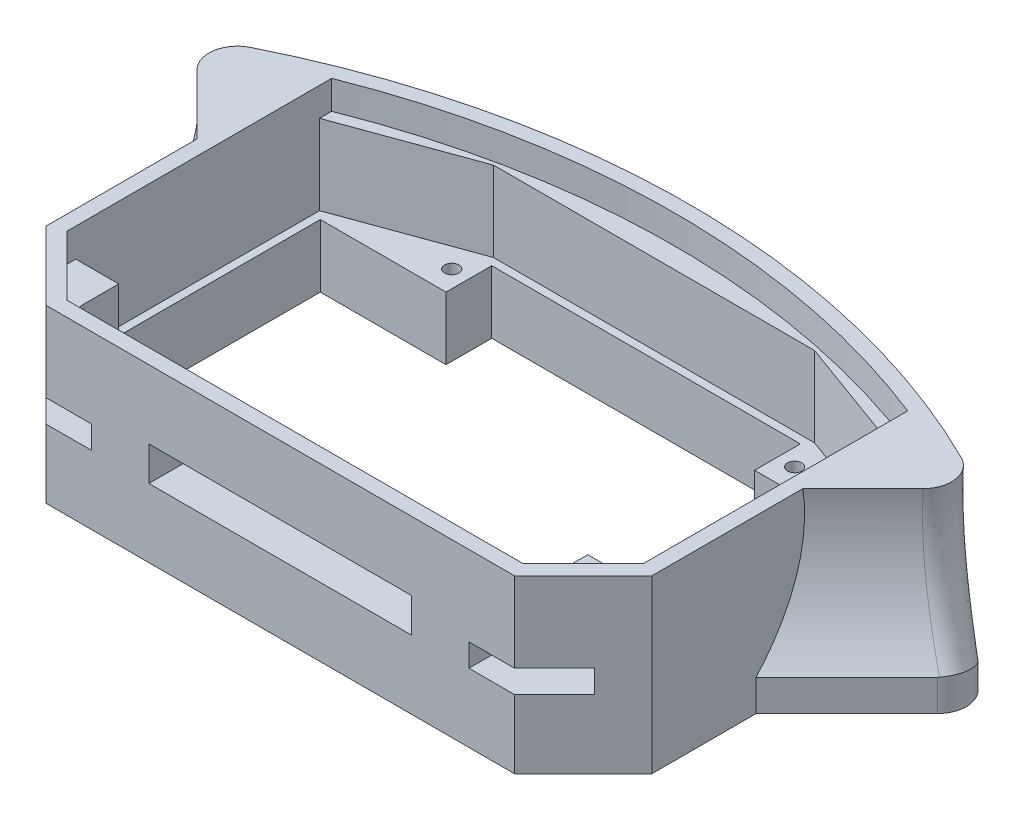
SolidWorks part; units mm, degrees
ref_plane "Front Plane" through (0, 0, 0) normal (0, 0, 1) x (1, 0, 0)
ref_plane "Top Plane" through (0, 0, 0) normal (0, 1, 0) x (1, 0, 0)
ref_plane "Right Plane" through (0, 0, 0) normal (1, 0, 0) x (0, 0, -1)
sketch "Sketch1" plane through (0, 0, 0) normal (0, 1, 0) x (1, 0, 0)
  line L0 (53, 80) -> (53, 129.1478)
  line L1 (-53, 129.1478) -> (-53, 80)
  line L2 (-41, 68) -> (41, 68)
  line L3 (-53, 80) -> (-41, 68)
  line L4 (41, 68) -> (53, 80)
  circle A0 centre (0, 0) radius 140 construction
  arc A1 (53, 129.1478) -> (-53, 129.1478) centre (0, 0) ccw
  dimension "D1" = 280
  dimension "D3" = 139.6
  dimension "D2" = 106
  dimension "D4" = 68
  dimension "D5" = 80
  dimension "D6" = 135
  dimension "D7" = 135
extrude "Boss-Extrude1" add sketch "Sketch1" along normal blind 30
sketch "Sketch2" plane through (0, 30, 0) normal (0, 1, 0) x (1, 0, 0)
  line L0 (-49, 84) -> (49, 84)
  line L1 (49, 84) -> (49, 124)
  line L2 (49, 124) -> (27, 124)
  line L3 (27, 124) -> (27, 132)
  line L4 (27, 132) -> (-27, 132)
  line L5 (-27, 132) -> (-27, 124)
  line L6 (-27, 124) -> (-49, 124)
  line L7 (-49, 124) -> (-49, 84)
  line L12 (-53, 129.1478) -> (-53, 80) construction
  dimension "D1" = 48
  dimension "D2" = 98
  dimension "D3" = 8
  dimension "D4" = 84
  dimension "D5" = 22
  dimension "D6" = 4
extrude "Cut-Extrude1" cut sketch "Sketch2" against normal up to next
sketch "Sketch3" plane through (0, 30, 0) normal (0, 1, 0) x (1, 0, 0)
  line L0 (-50, 83) -> (50, 83) construction
  line L1 (50, 83) -> (50, 125) construction
  line L2 (50, 125) -> (28, 133) construction
  line L3 (28, 133) -> (-28, 133) construction
  line L4 (-28, 133) -> (-50, 125) construction
  line L5 (-50, 125) -> (-50, 83) construction
  line L7 (-49, 84) -> (-49, 124) construction
  line L8 (-50.4, 125.2802) -> (-50.4, 82.6)
  line L9 (-50.4, 82.6) -> (50.4, 82.6)
  line L10 (50.4, 82.6) -> (50.4, 125.2802)
  line L11 (50.4, 125.2802) -> (28.0705, 133.4)
  line L12 (28.0705, 133.4) -> (-28.0705, 133.4)
  line L13 (-28.0705, 133.4) -> (-50.4, 125.2802)
  line L16 (-49, 84) -> (49, 84) construction
  dimension "D1" = 50
  dimension "D2" = 22
  dimension "D3" = 8
  dimension "D4" = 1
  dimension "D5" = 1
  dimension "D6" = 100
  dimension "D7" = 0.4
extrude "Cut-Extrude2" cut sketch "Sketch3" against normal offset from surface (19 mm away) 11 up to face at (0, 0, -116)
sketch "Sketch5" plane through (0, 30, 0) normal (0, 1, 0) x (1, 0, 0)
  line L1 (-42.48, 71.91) -> (38.8, 71.91) construction
  line L2 (-42.48, 71.91) -> (-42.48, 125.25) construction
  line L3 (-42.48, 125.25) -> (38.8, 125.25) construction
  line L4 (38.8, 71.91) -> (38.8, 125.25) construction
  line L6 (-42.88, 71.51) -> (-42.88, 125.65)
  line L7 (-42.88, 125.65) -> (39.2, 125.65)
  line L8 (39.2, 71.51) -> (39.2, 125.65)
  line L9 (-42.88, 71.51) -> (39.2, 71.51)
  dimension "D1" = 71.91
  dimension "D2" = 38.8
  dimension "D3" = 81.28
  dimension "D4" = 53.34
  dimension "D5" = 0.4
extrude "Cut-Extrude4" cut sketch "Sketch5" against normal offset from surface (12.4 mm away) 17.6 up to face at (0, 0, -116)
sketch "Sketch4" plane through (0, 17.6, 0) normal (0, 1, 0) x (1, 0, 0)
  circle A0 centre (26.18, 74.72) radius 1.25
  circle A1 centre (-27.53, 74.72) radius 1.25
  dimension "D2" = 2.5
  dimension "D1" = 27.53
  dimension "D3" = 5.28
  dimension "D4" = 26.18
extrude "Cut-Extrude3" cut sketch "Sketch4" against normal blind 15
fillet "Fillet1" radius 5 2 edges at (39.2, 23.8, -71.51) (-42.88, 23.8, -71.51)
sketch "Sketch6" plane through (0, 30, 0) normal (0, 1, 0) x (1, 0, 0)
  line L20 (50.4, 81.077) -> (50.4, 127.3925)
  line L21 (39.923, 70.6) -> (50.4, 81.077)
  line L22 (-39.923, 70.6) -> (39.923, 70.6)
  line L23 (-50.4, 81.077) -> (-39.923, 70.6)
  line L24 (-50.4, 127.3925) -> (-50.4, 81.077)
  line L25 (50.4, 81.077) -> (50.4, 127.3925)
  line L26 (39.923, 70.6) -> (50.4, 81.077)
  line L27 (-39.923, 70.6) -> (39.923, 70.6)
  line L28 (-50.4, 81.077) -> (-39.923, 70.6)
  line L29 (-50.4, 127.3925) -> (-50.4, 81.077)
  arc A7 (50.4, 127.3925) -> (-50.4, 127.3925) centre (0, 0) ccw
  arc A8 (50.4, 127.3925) -> (-50.4, 127.3925) centre (0, 0) ccw
  dimension "D1" = 2.6
extrude "Cut-Extrude5" cut sketch "Sketch6" against normal blind 5
sketch "Sketch7" plane through (0, 0, 0) normal (0, -1, 0) x (1, 0, 0)
  line L0 (73.4563, -118.7111) -> (53, -98.2548)
  line L1 (53, -80) -> (53, -129.1478) construction
  line L2 (53, -98.2548) -> (53, -129.1478)
  line L3 (0, 0) -> (103.3995, -103.3995) construction
  arc A0 (53, -129.1478) -> (73.4563, -118.7111) centre (0, 0) ccw
  arc A1 (-53, -129.1478) -> (53, -129.1478) centre (0, 0) ccw construction
  dimension "D1" = 45
  dimension "D2" = 32
extrude "Boss-Extrude2" add sketch "Sketch7" against normal up to surface (30 mm away) up to face at (0, 30, -94.6244)
ref_plane "Plane1" through (96.0837, 0, -96.0837) normal (-0.7071, 0, 0.7071) x (0, -1, 0)
sketch "Sketch8" plane through (96.0837, 0, -96.0837) normal (-0.7071, 0, 0.7071) x (0, -1, 0)
  line L0 (-30, -32) -> (0, -32) construction
  circle A0 centre (-26, 0) radius 38
  dimension "D3" = 76
  dimension "D1" = 32
  dimension "D2" = 26
extrude "Cut-Extrude6" cut sketch "Sketch8" along normal up to surface (98.9296 mm away) up to face at (53, 18.75, -84.5637)
mirror "Mirror1" about plane through (0, 0, 0) normal (1, 0, 0) of "Boss-Extrude2"
ref_plane "Plane2" through (-96.0837, 0, -96.0837) normal (0.7071, 0, 0.7071) x (0, -1, 0)
sketch "Sketch9" plane through (-96.0837, 0, -96.0837) normal (0.7071, 0, 0.7071) x (0, -1, 0)
  line L0 (-30, 32) -> (0, 32) construction
  circle A0 centre (-26, 0) radius 38
  dimension "D1" = 76
  dimension "D2" = 32
  dimension "D3" = 26
extrude "Cut-Extrude7" cut sketch "Sketch9" along normal up to surface (22.9296 mm away) up to face at (-53, 18.75, -93.6911)
fillet "Fillet2" radius 5 4 edges at (69.0949, 16.9868, -121.3015) (73.4563, 2.753, -118.7111) (-73.4563, 2.753, -118.7111) (-68.9598, 17.6248, -121.3784)
sketch "Sketch10" plane through (0, 0, -68) normal (0, 0, 1) x (1, 0, 0)
  line L0 (-41, 0) -> (41, 0) construction
  line L1 (-48, 16) -> (-33, 16)
  line L2 (-48, 16) -> (-48, 12)
  line L3 (-48, 12) -> (-33, 12)
  line L4 (-33, 16) -> (-33, 12)
  line L6 (-23, 12) -> (23, 12)
  line L7 (-23, 12) -> (-23, 18)
  line L8 (-23, 18) -> (23, 18)
  line L9 (23, 12) -> (23, 18)
  line L10 (33, 16) -> (48, 16)
  line L11 (33, 16) -> (33, 12)
  line L12 (33, 12) -> (48, 12)
  line L13 (48, 16) -> (48, 12)
  dimension "D1" = 12
  dimension "D2" = 15
  dimension "D3" = 48
  dimension "D4" = 4
  dimension "D5" = 96
  dimension "D6" = 10
  dimension "D7" = 10
  dimension "D8" = 6
extrude "Cut-Extrude8" cut sketch "Sketch10" against normal up to next
sketch "Sketch11" plane through (0, 11, 0) normal (0, 1, 0) x (1, 0, 0)
  line L0 (-49, 124) -> (-27, 124) construction
  circle A0 centre (-30, 128) radius 1.25
  circle A1 centre (30, 128) radius 1.25
  dimension "D2" = 2.5
  dimension "D1" = 4
  dimension "D3" = 60
  dimension "D4" = 30
extrude "Cut-Extrude9" cut sketch "Sketch11" against normal up to next
